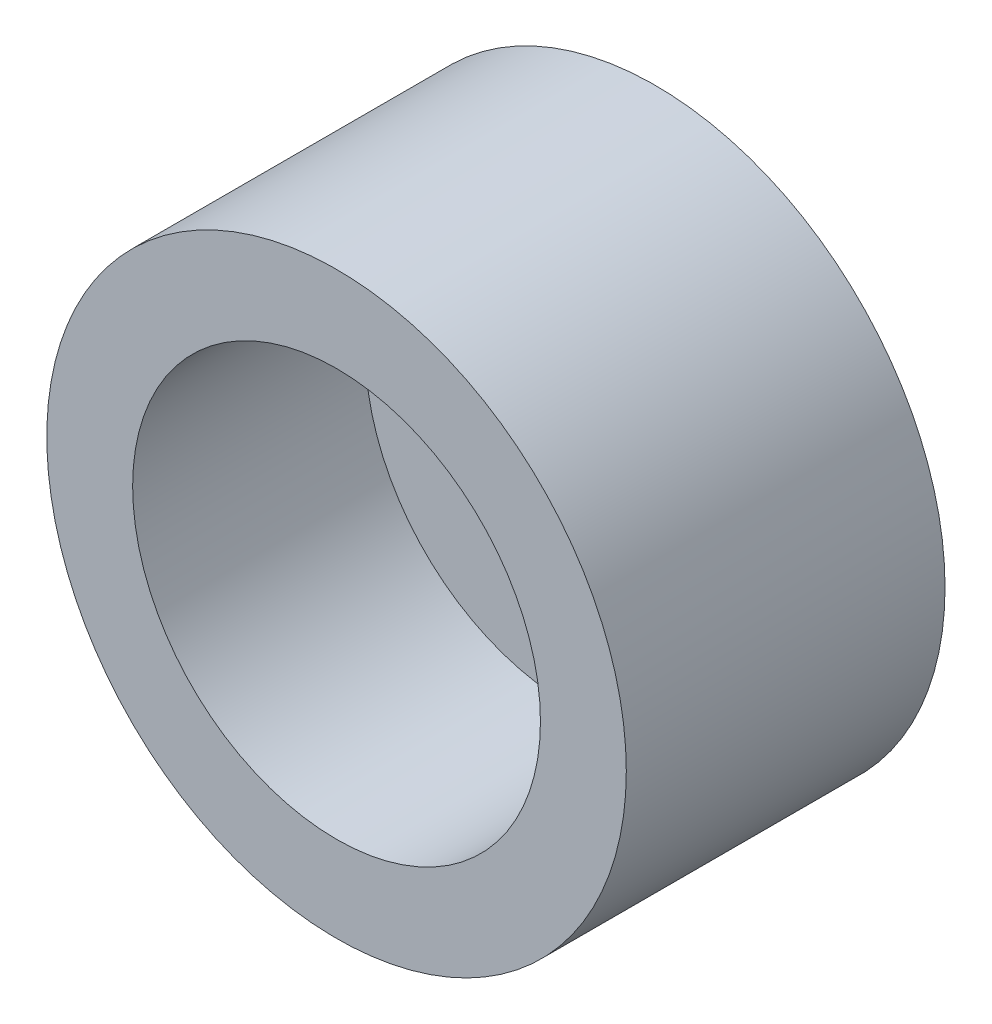
SolidWorks part; units mm, degrees
ref_plane "Front Plane" through (0, 0, 0) normal (0, 0, 1) x (1, 0, 0)
ref_plane "Top Plane" through (0, 0, 0) normal (0, 1, 0) x (1, 0, 0)
ref_plane "Right Plane" through (0, 0, 0) normal (1, 0, 0) x (0, 0, -1)
sketch "Sketch2" plane through (0, 0, 0) normal (0, 0, 1) x (1, 0, 0)
  circle A1 centre (0, 0) radius 7.5
  dimension "D2" = 15
extrude "Boss-Extrude1" add sketch "Sketch2" along normal blind 2
sketch "Sketch3" plane through (0, 0, 2) normal (0, 0, 1) x (1, 0, 0)
  circle A0 centre (0, 0) radius 4.75
  circle A1 centre (0, 0) radius 7.5
  dimension "D1" = 9.5
extrude "Boss-Extrude2" add sketch "Sketch3" along normal blind 5.425
sketch "Sketch4" plane through (0, 0, 7.425) normal (0, 0, 1) x (1, 0, 0)
  circle A0 centre (0, 0) radius 4.75
  circle A1 centre (0, 0) radius 6.75
  circle A2 centre (0, 0) radius 9.6335
  circle M1 centre (0, 0) radius 7.5
  dimension "D1" = 2
extrude "Cut-Extrude1" cut sketch "Sketch4" against normal through all contours A1 M1 region at (-7.2879, 0, 7.425)
